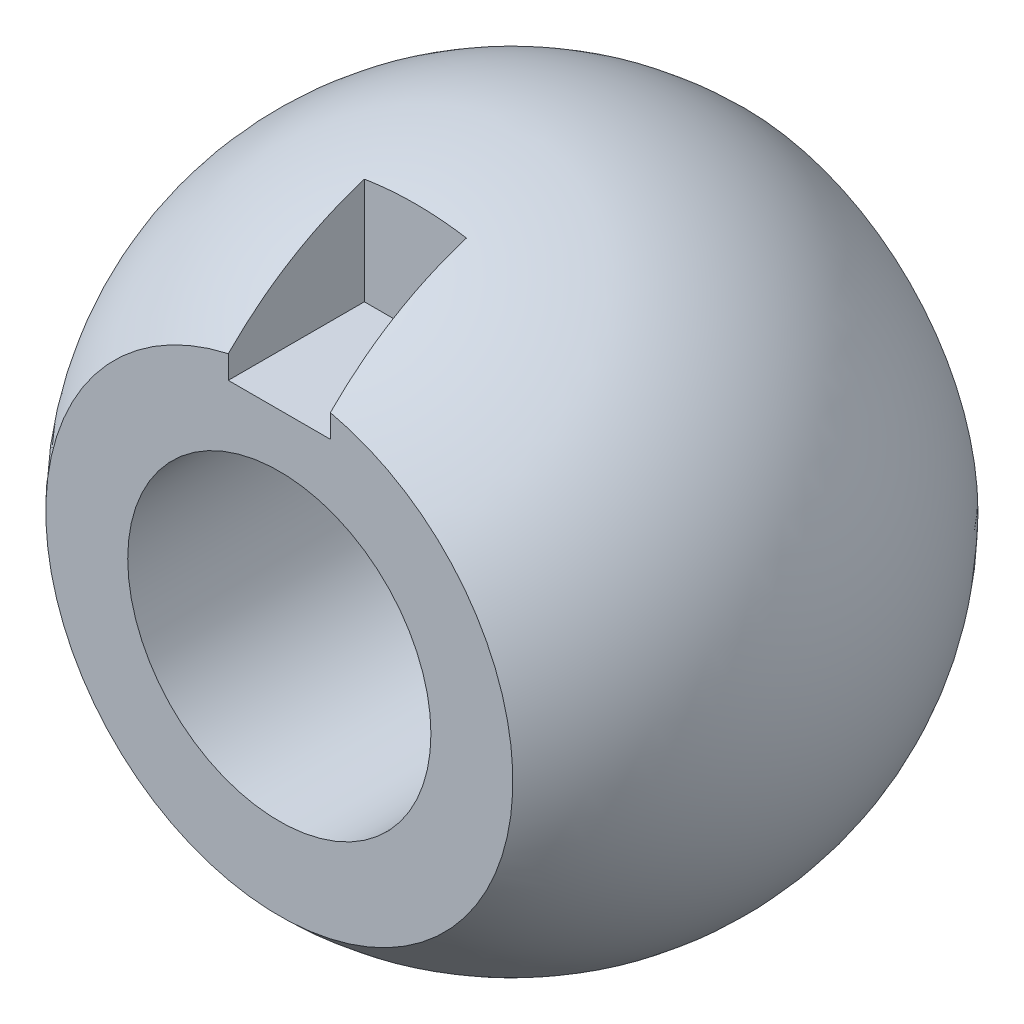
SolidWorks part; units mm, degrees
ref_plane "Front Plane" through (0, 0, 0) normal (0, 0, 1) x (1, 0, 0)
ref_plane "Top Plane" through (0, 0, 0) normal (0, 1, 0) x (1, 0, 0)
ref_plane "Right Plane" through (0, 0, 0) normal (1, 0, 0) x (0, 0, -1)
sketch "Sketch1" plane through (0, 0, 0) normal (0, 0, 1) x (1, 0, 0)
  line L0 (0, 7.874) -> (0, -7.874)
  arc A0 (0, 7.874) -> (0, -7.874) centre (0, 0) ccw
  dimension "CollarOD" = 7.874
revolve "Revolve1" add sketch "Sketch1" angle 360 about L0
sketch "Sketch2" plane through (0, 0, 0) normal (0, 0, 1) x (1, 0, 0)
  circle A0 centre (0, 0) radius 3.622
  dimension "CollarID" = 7.2441
extrude "Cut-Extrude1" cut sketch "Sketch2" along normal through all both and the other way through all
sketch "Sketch3" plane through (0, 0, 0) normal (0, 0, 1) x (1, 0, 0)
  circle A0 centre (0, 0) radius 15.748
extrude "Cut-Extrude2" cut sketch "Sketch3" along normal through all from offset 5.5562
extrude "Cut-Extrude3" cut sketch "Sketch3<2>" against normal through all from offset 5.5562 offset against normal yes
sketch "Sketch3<2>" plane through (0, 0, 0) normal (0, 0, 1) x (1, 0, 0) same geometry as "Sketch3"
sketch "Sketch4" plane through (0, 0, 5.5562) normal (0, 0, 1) x (1, 0, 0)
  line L3 (0, 4.892) -> (1.2192, 4.892)
  line L5 (0, 13.1664) -> (1.2192, 13.1664)
  line L6 (1.2192, 4.892) -> (1.2192, 13.1664)
  line L7 (0, 4.892) -> (-1.2192, 4.892)
  line L9 (0, 13.1664) -> (-1.2192, 13.1664)
  line L10 (-1.2192, 4.892) -> (-1.2192, 13.1664)
  dimension "NotchWidth" = 1.2192
  dimension "NochLength" = 4.892
extrude "Cut-Extrude4" cut sketch "Sketch4" against normal blind 3.2512
equation "\"NochLength@Sketch4\"= \"CollarID@Sketch2\" / 2 + 0.05"
